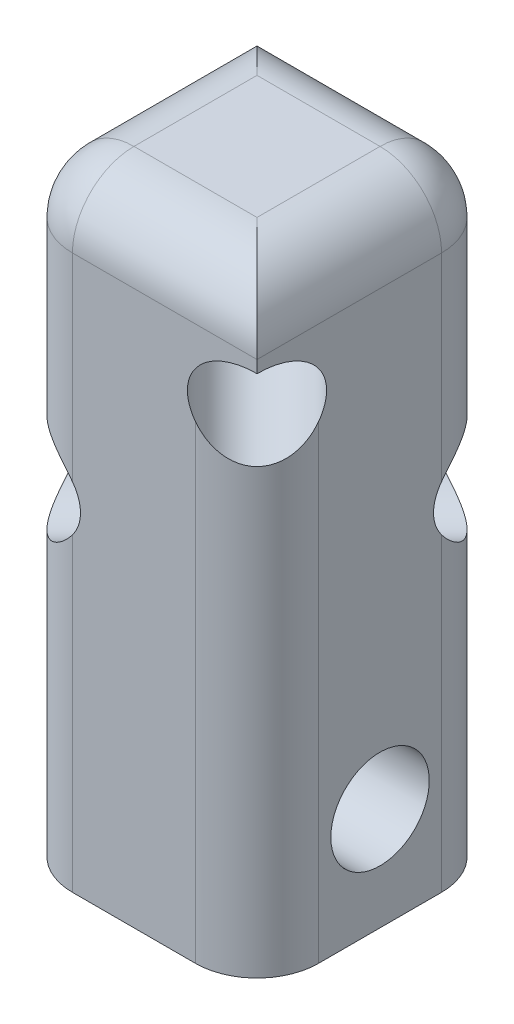
SolidWorks part; units mm, degrees
ref_plane "Front Plane" through (0, 0, 0) normal (0, 0, 1) x (1, 0, 0)
ref_plane "Top Plane" through (0, 0, 0) normal (0, 1, 0) x (1, 0, 0)
ref_plane "Right Plane" through (0, 0, 0) normal (1, 0, 0) x (0, 0, -1)
sketch "Sketch1" plane through (0, 0, 0) normal (0, 1, 0) x (1, 0, 0)
  line L1 (-3, -3) -> (3, -3)
  line L2 (-3, -3) -> (-3, 3)
  line L3 (-3, 3) -> (3, 3)
  line L4 (3, -3) -> (3, 3)
  line L5 (-3, -3) -> (3, 3) construction
  line L6 (-3, 3) -> (3, -3) construction
  point P0 (0, 0)
  dimension "D1" = 6
  dimension "D2" = 6
extrude "Boss-Extrude1" add sketch "Sketch1" along normal blind 15
sketch "Sketch2" plane through (-3, 0, 0) normal (-1, 0, 0) x (0, 0, 1)
  line L0 (-3, 0) -> (3, 0) construction
  line L2 (-3, 15) -> (3, 15) construction
  circle A0 centre (0, 2.51) radius 1.2
  point P7 (0, 15)
  dimension "D1" = 2.4
  dimension "D2" = 2.51
extrude "Cut-Extrude1" cut sketch "Sketch2" against normal blind 15
ref_axis "Axis1" through (3, 15, -3) along (-0.7071, 0, 0.7071)
ref_axis "Axis2" through (-3, 15, -3) along (0.7071, 0, 0.7071)
ref_plane "Plane1" through (3, 0, 3) normal (0.7071, 0, 0.7071) x (0.7071, 0, -0.7071)
sketch "Sketch3" plane through (3, 0, 3) normal (0.7071, 0, 0.7071) x (0.7071, 0, -0.7071)
  line L0 (0, 15) -> (0, 0) construction
  line L1 (-4.2426, 15) -> (0, 15) construction
  circle A0 centre (0, 12) radius 1.2
  dimension "D1" = 2.4
  dimension "D2" = 3
extrude "Cut-Extrude3" cut sketch "Sketch3" against normal blind 15
ref_plane "Plane2" through (-3, 0, 3) normal (-0.7071, 0, 0.7071) x (0.7071, 0, 0.7071)
sketch "Sketch4" plane through (-3, 0, 3) normal (-0.7071, 0, 0.7071) x (0.7071, 0, 0.7071)
  line L0 (0, 15) -> (0, 0) construction
  line L1 (0, 15) -> (4.2426, 15) construction
  circle A0 centre (0, 8.11) radius 1.2
  dimension "D1" = 2.4
  dimension "D2" = 6.89
extrude "Cut-Extrude5" cut sketch "Sketch4" against normal blind 15
fillet "Fillet1" radius 1.5 10 edges at (0, 15, 3) (-3, 15, 0) (0, 15, -3) (3, 15, 0) (-3, 12.155, 3) (-3, 3.455, 3) (3, 5.4, 3) (3, 3.455, -3) (3, 12.155, -3) (-3, 5.4, -3)
